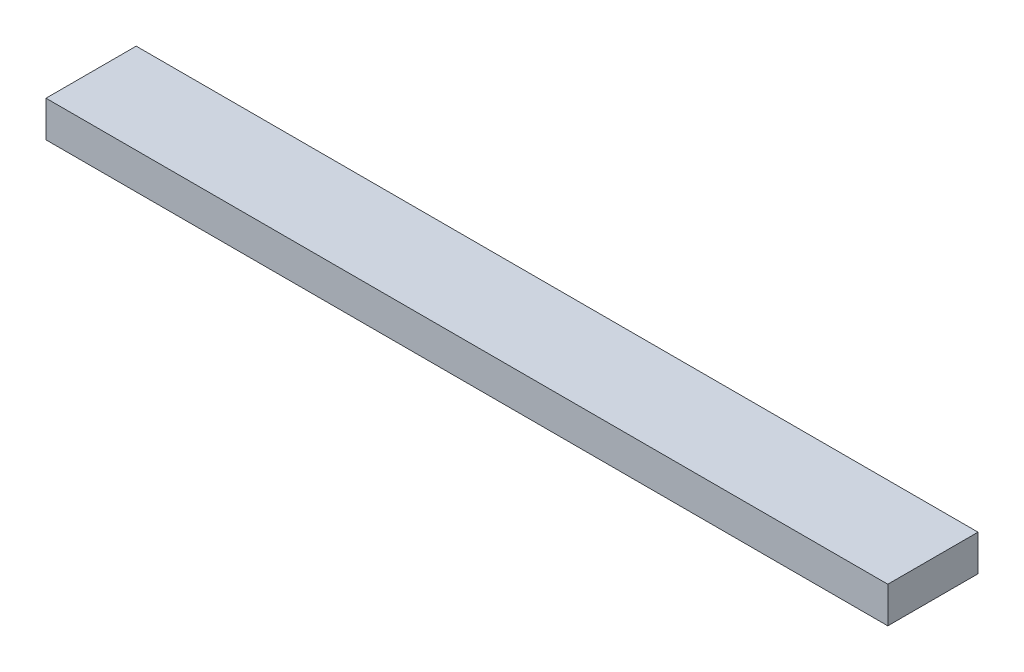
SolidWorks part; units mm, degrees
ref_plane "Front Plane" through (0, 0, 0) normal (0, 0, 1) x (1, 0, 0)
ref_plane "Top Plane" through (0, 0, 0) normal (0, 1, 0) x (1, 0, 0)
ref_plane "Right Plane" through (0, 0, 0) normal (1, 0, 0) x (0, 0, -1)
sketch "Sketch1" plane through (0, 0, 0) normal (0, 1, 0) x (1, 0, 0)
  line L1 (-70, 7.5) -> (70, 7.5)
  line L2 (-70, 7.5) -> (-70, -7.5)
  line L3 (-70, -7.5) -> (70, -7.5)
  line L4 (70, 7.5) -> (70, -7.5)
  line L5 (-70, 7.5) -> (70, -7.5) construction
  line L6 (-70, -7.5) -> (70, 7.5) construction
  point P0 (0, 0)
  dimension "D1" = 140
  dimension "D2" = 15
extrude "Boss-Extrude1" add sketch "Sketch1" along normal blind 6
